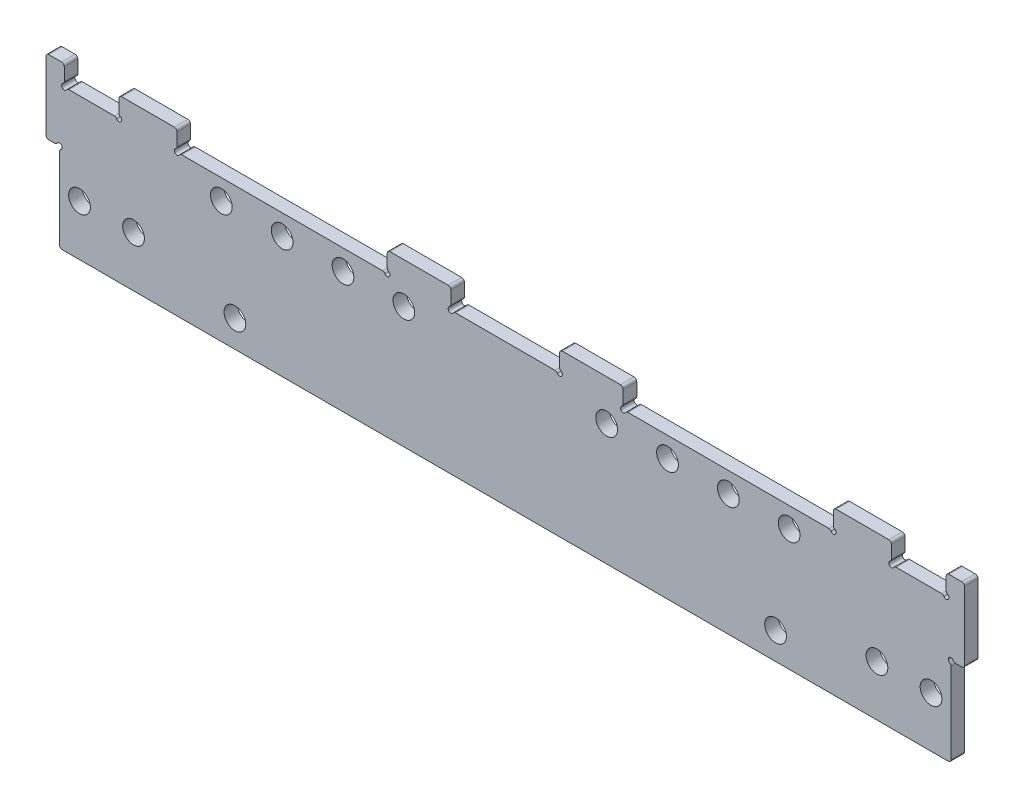
SolidWorks part; units mm, degrees
material "AISI Type A2 Tool Steel"
ref_plane "Front Plane" through (0, 0, 0) normal (0, 0, 1) x (1, 0, 0)
ref_plane "Top Plane" through (0, 0, 0) normal (0, 1, 0) x (1, 0, 0)
ref_plane "Right Plane" through (0, 0, 0) normal (1, 0, 0) x (0, 0, -1)
sketch "Top Layout" plane through (0, 0, 0) normal (0, 1, 0) x (1, 0, 0)
  line L0 (-114.046, -123.825) -> (-104.775, -123.825) construction
  line L1 (-104.775, -142.875) -> (-101.6, -142.875)
  line L2 (-104.775, -142.875) -> (-104.775, -104.775)
  line L3 (-104.775, -104.775) -> (-101.6, -104.775)
  line L4 (-101.6, -142.875) -> (-101.6, -104.775)
  line L5 (-104.775, -142.875) -> (-101.6, -104.775) construction
  line L6 (-104.775, -104.775) -> (-101.6, -142.875) construction
  line L7 (-19.05, -105.8164) -> (-101.6, -105.8164)
  line L8 (-19.05, -105.8164) -> (-19.05, -141.8336)
  line L9 (-19.05, -141.8336) -> (-101.6, -141.8336)
  line L10 (-101.6, -105.8164) -> (-101.6, -141.8336)
  line L11 (-19.05, -105.8164) -> (-101.6, -141.8336) construction
  line L12 (-19.05, -141.8336) -> (-101.6, -105.8164) construction
  line L13 (-133.096, -85.725) -> (-114.046, -85.725)
  line L14 (-133.096, -85.725) -> (-133.096, -161.925)
  line L15 (-133.096, -161.925) -> (-114.046, -161.925)
  line L16 (-114.046, -85.725) -> (-114.046, -161.925)
  line L17 (-133.096, -85.725) -> (-114.046, -161.925) construction
  line L18 (-133.096, -161.925) -> (-114.046, -85.725) construction
  line L19 (-104.775, -123.825) -> (0, -123.825) construction
  line L20 (0, -123.825) -> (0, 0) construction
  line L21 (-52.3528, -40.1717) -> (0, 0) construction
  line L22 (-70.6449, -16.3328) -> (-18.2922, 23.8388)
  line L23 (-34.0606, -64.0105) -> (18.2922, -23.8388)
  line L24 (-30.9251, 40.3023) -> (-122.2248, -29.7544)
  line L25 (-153.9748, -53.975) -> (-153.9748, -123.825)
  line L26 (-109.5248, -162.052) -> (109.5248, -162.052)
  line L27 (0, -162.052) -> (0, -123.825) construction
  line L28 (-109.5248, -162.052) -> (-109.5248, -20.0093) construction
  line L29 (-104.775, -142.875) -> (-104.775, -152.527)
  line L30 (-104.775, -152.527) -> (104.775, -152.527)
  line L31 (104.775, -104.775) -> (101.6, -104.775)
  line L32 (-144.4498, -73.025) -> (-109.5248, -73.025)
  line L33 (-144.4498, -73.025) -> (-144.4498, -123.825)
  line L34 (-144.4498, -123.825) -> (-109.5248, -123.825) construction
  line L35 (-109.5248, -73.025) -> (-109.5248, -162.052)
  line L36 (-144.4498, -73.025) -> (-109.5248, -123.825) construction
  line L37 (-144.4498, -123.825) -> (-109.5248, -73.025) construction
  line L38 (101.6, -142.875) -> (101.6, -104.775)
  line L39 (104.775, -142.875) -> (101.6, -142.875)
  line L40 (104.775, -142.875) -> (104.775, -104.775)
  line L41 (104.775, -142.875) -> (104.775, -152.527)
  line L42 (109.5248, -162.052) -> (109.5248, -20.0093) construction
  line L43 (30.9251, 40.3023) -> (122.2248, -29.7544)
  line L45 (19.05, -141.8336) -> (101.6, -141.8336)
  line L46 (101.6, -105.8164) -> (101.6, -141.8336)
  line L47 (19.05, -105.8164) -> (101.6, -105.8164)
  line L48 (19.05, -105.8164) -> (19.05, -141.8336)
  line L49 (133.096, -161.925) -> (114.046, -161.925)
  line L50 (114.046, -85.725) -> (114.046, -161.925)
  line L51 (133.096, -85.725) -> (114.046, -85.725)
  line L52 (133.096, -85.725) -> (133.096, -161.925)
  line L53 (144.4498, -123.825) -> (109.5248, -123.825) construction
  line L54 (109.5248, -73.025) -> (109.5248, -162.052)
  line L55 (144.4498, -73.025) -> (109.5248, -73.025)
  line L56 (144.4498, -73.025) -> (144.4498, -123.825)
  line L57 (-109.5248, -123.825) -> (-109.5248, -162.052) construction
  line L62 (-153.9748, -53.975) -> (-122.2248, -53.975)
  line L63 (-122.2248, -53.975) -> (-122.2248, -29.7544)
  line L64 (-144.4498, -123.825) -> (-153.9748, -123.825)
  line L65 (153.9748, -53.975) -> (153.9748, -123.825)
  line L66 (109.5248, -123.825) -> (109.5248, -162.052) construction
  line L67 (144.4498, -123.825) -> (153.9748, -123.825)
  line L68 (122.2248, -29.7544) -> (122.2248, -53.975)
  line L73 (-104.775, -104.775) -> (-104.775, -16.3647) construction
  line L74 (-95.25, -162.052) -> (-95.25, -9.0559) construction
  line L75 (-109.5248, -162.052) -> (-109.5248, -123.825) construction
  line L76 (109.5248, -162.052) -> (109.5248, -123.825) construction
  line L77 (122.2248, -53.975) -> (153.9748, -53.975)
  line L83 (104.775, -155.5496) -> (-104.775, -155.5496) construction
  line L88 (95.25, -162.052) -> (95.25, -9.0559) construction
  line L89 (104.775, -104.775) -> (104.775, -16.3647) construction
  line L92 (-104.775, -152.527) -> (-104.775, -162.052) construction
  line L93 (-14.605, -76.327) -> (14.605, -76.327)
  line L94 (-14.605, -76.327) -> (-14.605, -152.527)
  line L95 (-14.605, -152.527) -> (14.605, -152.527)
  line L96 (14.605, -76.327) -> (14.605, -152.527)
  line L97 (-14.605, -76.327) -> (14.605, -152.527) construction
  line L98 (-14.605, -152.527) -> (14.605, -76.327) construction
  line L99 (104.775, -152.527) -> (104.775, -162.052) construction
  line L100 (-19.05, -105.8164) -> (0, -105.8164) construction
  line L107 (0, -105.8164) -> (19.05, -105.8164) construction
  line L108 (104.775, -123.825) -> (114.046, -123.825) construction
  circle A0 centre (0, 0) radius 114.3
  circle A1 centre (0, 0) radius 6.35
  circle A2 centre (-52.3528, -40.1717) radius 17.8
  circle A3 centre (0, 0) radius 30.0482
  circle A4 centre (-52.3528, -40.1717) radius 30.0482
  arc A5 (-30.9251, 40.3023) -> (30.9251, 40.3023) centre (0, 0) cw
  point P2 (-103.1875, -123.825)
  point P7 (-60.325, -123.825)
  point P12 (-123.571, -123.825)
  point P30 (-126.9873, -98.425)
  point P35 (0, -114.427)
  point P53 (0, -152.527)
  dimension "D1" = 35.6
  dimension "D2" = 12.7
  dimension "D3" = 228.6
  dimension "D11" = 60.0964
  dimension "D12" = 50.8
  dimension "D14" = 52.5
  dimension "D4" = 3.175
  dimension "D5" = 19.05
  dimension "D6" = 76.2
  dimension "D7" = 82.55
  dimension "D8" = 38.1
  dimension "D9" = 104.775
  dimension "D10" = 18.0086
  dimension "D13" = 9.525
  dimension "D15" = 4.7498
  dimension "D16" = 9.525
  dimension "D17" = 9.652
  dimension "D18" = 50.8
  dimension "D19" = 12.446
  dimension "D20" = 65.9892
  dimension "D21" = 19.05
  dimension "D22" = 34.925
  dimension "D23" = 123.825
  dimension "D24" = 12.7
  dimension "D25" = 9.525
  dimension "D26" = 29.21
  dimension "D27" = 76.2
  dimension "D28" = 3.0226
sketch "Side Layout" plane through (0, 0, 0) normal (1, 0, 0) x (0, 0, -1)
  line L0 (0, -38.1) -> (0, 33.7344) construction
  line L1 (-114.3, -20.955) -> (114.3, -20.955)
  line L2 (-114.3, -20.955) -> (-114.3, -33.655)
  line L3 (-114.3, -33.655) -> (114.3, -33.655)
  line L4 (114.3, -20.955) -> (114.3, -33.655)
  line L5 (-114.3, -20.955) -> (114.3, -33.655) construction
  line L6 (-114.3, -33.655) -> (114.3, -20.955) construction
  line L7 (-9.525, -32.9406) -> (9.525, -32.9406)
  line L8 (-9.525, -32.9406) -> (-9.525, -38.1)
  line L9 (-9.525, -38.1) -> (9.525, -38.1)
  line L10 (9.525, -32.9406) -> (9.525, -38.1)
  line L11 (-9.525, -32.9406) -> (9.525, -38.1) construction
  line L12 (-9.525, -38.1) -> (9.525, -32.9406) construction
  line L13 (-11.9126, -29.3338) -> (11.9126, -29.3338)
  line L14 (-11.9126, -29.3338) -> (-11.9126, -32.9406)
  line L15 (-11.9126, -32.9406) -> (11.9126, -32.9406)
  line L16 (11.9126, -29.3338) -> (11.9126, -32.9406)
  line L17 (-11.9126, -29.3338) -> (11.9126, -32.9406) construction
  line L18 (-11.9126, -32.9406) -> (11.9126, -29.3338) construction
  line L19 (-6.35, -32.9406) -> (6.35, -32.9406)
  line L20 (-6.35, -32.9406) -> (-6.35, 33.7344)
  line L21 (-6.35, 33.7344) -> (6.35, 33.7344)
  line L22 (6.35, -32.9406) -> (6.35, 33.7344)
  line L23 (-6.35, -32.9406) -> (6.35, 33.7344) construction
  line L24 (-6.35, 33.7344) -> (6.35, -32.9406) construction
  line L25 (-162.052, 0) -> (-123.825, 0) construction
  line L26 (114.3, -33.655) -> (114.3, 0) construction
  line L27 (-142.875, 19.05) -> (-104.775, 19.05)
  line L28 (-40.1717, -9.525) -> (-40.1717, 5.4) construction
  line L29 (-142.875, 19.05) -> (-142.875, -19.05)
  line L30 (-142.875, -19.05) -> (-104.775, -19.05)
  line L31 (-104.775, 19.05) -> (-104.775, -19.05)
  line L32 (-142.875, 19.05) -> (-104.775, -19.05) construction
  line L33 (-142.875, -19.05) -> (-104.775, 19.05) construction
  line L34 (-130.175, -38.1) -> (-117.9516, -38.1) construction
  line L35 (-57.9717, -14.6) -> (-22.3717, -14.6)
  line L36 (-30.0482, -2.794) -> (30.0482, -2.794)
  line L37 (-30.0482, -2.794) -> (-30.0482, -20.955)
  line L38 (-30.0482, -20.955) -> (30.0482, -20.955)
  line L39 (30.0482, -2.794) -> (30.0482, -20.955)
  line L40 (-30.0482, -2.794) -> (30.0482, -20.955) construction
  line L41 (-30.0482, -20.955) -> (30.0482, -2.794) construction
  line L42 (-30.0482, -2.794) -> (-30.0482, 0) construction
  line L43 (-123.825, 0) -> (0, 0) construction
  line L44 (-57.9717, -14.6) -> (-57.9717, 25.4)
  line L45 (-57.9717, 25.4) -> (-22.3717, 25.4)
  line L46 (-22.3717, -14.6) -> (-22.3717, 25.4)
  line L47 (-19.05, 0) -> (19.05, 0)
  line L48 (-19.05, 0) -> (-19.05, -1.9812)
  line L49 (-19.05, -1.9812) -> (19.05, -1.9812)
  line L50 (19.05, 0) -> (19.05, -1.9812)
  line L51 (-19.05, 0) -> (19.05, -1.9812) construction
  line L52 (-19.05, -1.9812) -> (19.05, 0) construction
  line L53 (-70.2199, -3.175) -> (-10.1235, -3.175)
  line L54 (-70.2199, -3.175) -> (-70.2199, -15.875)
  line L55 (-70.2199, -15.875) -> (-10.1235, -15.875)
  line L56 (-10.1235, -3.175) -> (-10.1235, -15.875)
  line L57 (-70.2199, -3.175) -> (-10.1235, -15.875) construction
  line L58 (-70.2199, -15.875) -> (-10.1235, -3.175) construction
  line L59 (-40.1717, -9.525) -> (-40.1717, 0) construction
  line L60 (-57.9717, -14.6) -> (-22.3717, 25.4) construction
  line L61 (-57.9717, 25.4) -> (-22.3717, -14.6) construction
  line L62 (-22.3717, 0) -> (-57.9717, 0) construction
  line L63 (-137.8162, 0) -> (-123.825, -13.9912) construction
  line L64 (-139.065, 15.24) -> (-108.585, 15.24) construction
  line L65 (-139.065, 15.24) -> (-139.065, -15.24) construction
  line L66 (-139.065, -15.24) -> (-108.585, -15.24) construction
  line L67 (-108.585, 15.24) -> (-108.585, -15.24) construction
  line L68 (-139.065, 15.24) -> (-108.585, -15.24) construction
  line L69 (-139.065, -15.24) -> (-108.585, 15.24) construction
  line L70 (-137.8162, 0) -> (-123.825, 13.9912) construction
  line L71 (-123.825, -13.9912) -> (-109.8338, 0) construction
  line L72 (-123.825, 13.9912) -> (-109.8338, 0) construction
  line L73 (-137.8162, 0) -> (-109.8338, 0) construction
  line L74 (-123.825, -13.9912) -> (-123.825, 13.9912) construction
  line L75 (-6.35, 17.8594) -> (6.35, 17.8594)
  line L76 (114.3, 0) -> (-114.3, 0) construction
  line L77 (-22.3717, 19.05) -> (-6.35, 19.05) construction
  line L78 (-123.825, 38.1) -> (-97.9206, 38.1) construction
  line L79 (-19.05, -3.5814) -> (19.05, -3.5814)
  line L80 (-19.05, -3.5814) -> (-19.05, -1.9812)
  line L81 (-19.05, -1.9812) -> (19.05, -1.9812)
  line L82 (19.05, -3.5814) -> (19.05, -1.9812)
  line L83 (-19.05, -3.5814) -> (19.05, -1.9812) construction
  line L84 (-19.05, -1.9812) -> (19.05, -3.5814) construction
  line L85 (-8.7376, -16.7608) -> (8.7376, -16.7608)
  line L86 (-8.7376, -16.7608) -> (-8.7376, -29.3338)
  line L87 (-8.7376, -29.3338) -> (8.7376, -29.3338)
  line L88 (8.7376, -16.7608) -> (8.7376, -29.3338)
  line L89 (-8.7376, -16.7608) -> (8.7376, -29.3338) construction
  line L90 (-8.7376, -29.3338) -> (8.7376, -16.7608) construction
  line L91 (-8.7376, -3.5814) -> (8.7376, -3.5814)
  line L92 (-8.7376, -3.5814) -> (-8.7376, -16.1544)
  line L93 (-8.7376, -16.1544) -> (8.7376, -16.1544)
  line L94 (8.7376, -3.5814) -> (8.7376, -16.1544)
  line L95 (-8.7376, -3.5814) -> (8.7376, -16.1544) construction
  line L96 (-8.7376, -16.1544) -> (8.7376, -3.5814) construction
  circle A0 centre (-123.825, 0) radius 18.0086
  circle A1 centre (-123.825, 0) radius 38.1
  circle A2 centre (-139.065, 15.24) radius 1.905
  circle A3 centre (-108.585, 15.24) radius 1.905
  circle A4 centre (-108.585, -15.24) radius 1.905
  circle A5 centre (-139.065, -15.24) radius 1.905
  circle A6 centre (-137.8162, 0) radius 1.6002
  circle A7 centre (-123.825, 13.9912) radius 1.6002
  circle A8 centre (-109.8338, 0) radius 1.6002
  circle A9 centre (-123.825, -13.9912) radius 1.6002
  point P0 (0, -27.305)
  point P6 (0, -31.1372)
  point P7 (0, -35.5203)
  point P21 (0, 0.3969)
  point P32 (0, -11.8745)
  point P43 (0, -0.9906)
  point P55 (-40.1717, -9.525)
  point P72 (-40.1717, 5.4)
  point P88 (0, -23.0473)
  point P93 (0, -2.7813)
  point P102 (0, -9.8679)
  dimension "D17" = 3.81
  dimension "D18" = 3.2004
  dimension "D1" = 12.7
  dimension "D2" = 5.1594
  dimension "D3" = 19.05
  dimension "D4" = 3.6068
  dimension "D5" = 23.8252
  dimension "D6" = 12.7
  dimension "D7" = 18.161
  dimension "D8" = 1.9812
  dimension "D9" = 12.7
  dimension "D10" = 40
  dimension "D11" = 25.4
  dimension "D12" = 50.8
  dimension "D13" = 41.275
  dimension "D14" = 30.48
  dimension "D15" = 4.445
  dimension "D16" = 19.7866
  dimension "D19" = 15.875
  dimension "D20" = 6.35
  dimension "D21" = 38.1
  dimension "D22" = 1.6002
  dimension "D23" = 38.1
  dimension "D24" = 17.4752
  dimension "D25" = 12.573
ref_plane "Plane1" through (0, 25.4, 0) normal (0, 1, 0) x (1, 0, 0)
sketch "Sketch3" plane through (0, 25.4, 0) normal (0, 1, 0) x (1, 0, 0)
  line L0 (-104.775, -36.3747) -> (-30.9251, 20.2924)
  line L1 (-104.775, -104.775) -> (-104.775, -16.3647) construction
  line L2 (0, -200130.175) -> (0, 199882.0484) construction
  line L3 (-30.9251, 40.3023) -> (-122.2248, -29.7544) construction
  line L5 (-104.775, -36.3747) -> (-104.775, -77.6497)
  line L6 (-92.075, -77.6497) -> (-104.775, -77.6497)
  line L7 (30.9251, 20.2924) -> (104.775, -36.3747)
  line L8 (104.775, -77.6497) -> (92.075, -77.6497)
  line L9 (104.775, -36.3747) -> (104.775, -77.6497)
  line L11 (104.775, -104.775) -> (104.775, -16.3647) construction
  line L12 (30.9251, 40.3023) -> (122.2248, -29.7544) construction
  line L13 (92.075, -74.6536) -> (24.1423, -22.5271)
  line L14 (-32.2514, -66.3682) -> (20.1013, -26.1965)
  line L15 (-30.9251, 20.2924) -> (0, 44.022)
  line L16 (0, 44.022) -> (30.9251, 20.2924)
  line L17 (-92.075, -77.6497) -> (-92.075, -73.1917)
  line L19 (-92.075, -73.1917) -> (-52.3528, -73.1917)
  line L20 (92.075, -74.6536) -> (92.075, -77.6497)
  circle A0 centre (-52.3528, -40.1717) radius 17.8 construction
  circle A1 centre (-52.3528, -40.1717) radius 17.8
  circle A2 centre (0, 0) radius 6.35
  circle A3 centre (0, 0) radius 6.35 construction
  arc A4 (-52.3528, -73.1917) -> (-32.2514, -66.3682) centre (-52.3528, -40.1717) ccw
  arc A5 (20.1013, -26.1965) -> (24.1423, -22.5271) centre (0, 0) ccw
  arc A6 (30.9251, 20.2924) -> (-30.9251, 20.2924) centre (0, -20.01) ccw construction
  point P28 (0, 44.022)
  dimension "D1" = 33.02
  dimension "D5" = 50.8
  dimension "D2" = 41.275
  dimension "D3" = 34.925
  dimension "D4" = 12.7
  dimension "D6" = 38.1
ref_plane "Plane3" through (-104.775, 0, 0) normal (-1, 0, 0) x (0, 0, 1)
sketch "Sketch6" plane through (-104.775, 0, 0) normal (-1, 0, 0) x (0, 0, 1)
  line L0 (162.052, -25.4) -> (162.052, 25.4)
  line L1 (162.052, 25.4) -> (77.6497, 25.4)
  line L2 (36.3747, 25.4) -> (77.6497, 25.4) construction
  line L3 (147.7645, 11.1125) -> (162.052, 11.1125) construction
  line L4 (162.052, 0) -> (71.2997, 0) construction
  line L5 (77.6497, 25.4) -> (77.6497, 19.05)
  line L6 (77.6497, 19.05) -> (36.3747, 19.05)
  line L7 (36.3747, 19.05) -> (36.3747, 6.35)
  line L8 (36.3747, 6.35) -> (71.2997, 6.35)
  line L10 (99.6315, -3.175) -> (99.6315, 11.1125) construction
  line L11 (71.2997, -25.4) -> (162.052, -25.4)
  line L13 (71.2997, 6.35) -> (71.2997, -25.4)
  line L14 (152.527, -25.4) -> (152.527, 25.4) construction
  line L15 (99.6315, 11.1125) -> (99.6315, 25.4) construction
  line L16 (147.7645, 11.1125) -> (147.7645, 25.4) construction
  line L17 (94.869, -7.9375) -> (104.394, -7.9375) construction
  line L18 (94.869, -7.9375) -> (94.869, 25.4) construction
  line L19 (94.869, 25.4) -> (104.394, 25.4) construction
  line L20 (104.394, -7.9375) -> (104.394, 25.4) construction
  line L21 (94.869, -7.9375) -> (104.394, 25.4) construction
  line L22 (94.869, 25.4) -> (104.394, -7.9375) construction
  line L23 (147.7645, 11.1125) -> (147.7645, -3.175) construction
  line L24 (104.394, -7.9375) -> (123.825, -7.9375) construction
  line L25 (143.002, -7.9375) -> (152.527, -7.9375) construction
  line L26 (143.002, -7.9375) -> (143.002, 25.4) construction
  line L27 (143.002, 25.4) -> (152.527, 25.4) construction
  line L28 (152.527, -7.9375) -> (152.527, 25.4) construction
  line L29 (143.002, -7.9375) -> (152.527, 25.4) construction
  line L30 (143.002, 25.4) -> (152.527, -7.9375) construction
  line L31 (123.825, -7.9375) -> (152.527, -7.9375) construction
  line L32 (104.775, 19.05) -> (104.775, -19.05) construction
  line L34 (155.702, -25.4) -> (155.702, 25.4) construction
  circle A0 centre (109.8338, 0) radius 1.6002 construction
  circle A1 centre (123.825, 13.9912) radius 1.6002 construction
  circle A2 centre (137.8162, 0) radius 1.6002 construction
  circle A3 centre (123.825, -13.9912) radius 1.6002 construction
  circle A4 centre (109.8338, 0) radius 1.6002 construction
  circle A5 centre (123.825, 13.9912) radius 1.6002 construction
  circle A6 centre (137.8162, 0) radius 1.6002 construction
  circle A7 centre (123.825, -13.9912) radius 1.6002 construction
  circle A8 centre (123.825, 0) radius 18.0086 construction
  circle A9 centre (123.825, 0) radius 18.0086 construction
  circle A10 centre (123.825, 0) radius 9.525
  circle A11 centre (108.585, -15.24) radius 1.905 construction
  circle A12 centre (108.585, 15.24) radius 1.905 construction
  circle A13 centre (139.065, 15.24) radius 1.905 construction
  circle A14 centre (139.065, -15.24) radius 1.905 construction
  circle A15 centre (108.585, -15.24) radius 1.905
  circle A16 centre (108.585, 15.24) radius 1.905
  circle A17 centre (139.065, 15.24) radius 1.905
  circle A18 centre (139.065, -15.24) radius 1.905
  circle A19 centre (147.7645, 11.1125) radius 2.5527
  circle A26 centre (99.6315, 11.1125) radius 2.5527
  circle A27 centre (99.6315, -3.175) radius 2.5527
  circle A28 centre (147.7645, -3.175) radius 2.5527
  point P29 (0, 0)
  point P55 (99.6315, 8.7312)
  point P61 (147.7645, 8.7312)
  dimension "D4" = 19.05
  dimension "D7" = 5.1054
  dimension "D1" = 6.35
  dimension "D2" = 12.7
  dimension "D3" = 25.4
  dimension "D5" = 6.35
  dimension "D6" = 3.175
  dimension "D8" = 0.381
  dimension "D9" = 14.2875
  dimension "D10" = 9.525
  dimension "D12" = 33.3375
ref_plane "Plane4" through (0, 19.05, 0) normal (0, 1, 0) x (1, 0, 0)
sketch "Sketch12" plane through (0, 19.05, 0) normal (0, 1, 0) x (1, 0, 0)
  line L0 (-104.775, -77.6497) -> (-104.775, -36.3747)
  line L1 (-104.775, -36.3747) -> (-92.075, -36.3747)
  line L3 (-92.075, -36.3747) -> (-92.075, -77.6497)
  line L5 (-92.075, -77.6497) -> (-104.775, -77.6497)
  line L6 (-98.425, -77.6497) -> (-98.425, -63.3622) construction
  line L7 (-98.425, -63.3622) -> (-98.425, -50.6622) construction
  line L8 (-98.425, -50.6622) -> (-98.425, -36.3747) construction
  line L10 (-98.425, -36.3747) -> (-104.775, -36.3747) construction
  circle A0 centre (-98.425, -63.3622) radius 2.5527
  circle A1 centre (-98.425, -50.6622) radius 2.5527
  dimension "D2" = 5.1054
  dimension "D1" = 12.7
  dimension "D3" = 12.7
ref_plane "Plane5" through (0, 0, 152.527) normal (0, 0, 1) x (1, 0, 0)
sketch "Sketch41" plane through (0, 0, 152.527) normal (0, 0, 1) x (1, 0, 0)
  line L0 (-104.775, -7.9375) -> (-104.775, 25.4) construction
  line L1 (-104.775, -7.9375) -> (-104.775, 12.7)
  line L2 (-104.775, -7.9375) -> (104.775, -7.9375)
  line L3 (104.775, -7.9375) -> (104.775, 12.7)
  line L4 (104.775, 25.4) -> (-104.775, 25.4)
  line L5 (0, -7.9375) -> (0, 25.4) construction
  line L6 (-104.775, 3.9624) -> (-100.0125, 3.9624) construction
  line L7 (-100.0125, 3.9624) -> (-100.0125, 25.4) construction
  line L8 (104.775, 3.9624) -> (100.0125, 3.9624) construction
  line L9 (100.0125, 3.9624) -> (100.0125, 25.4) construction
  line L10 (19.05, 20.6375) -> (23.8252, 20.6375) construction
  line L11 (19.05, 15.875) -> (78.5876, 15.875) construction
  line L12 (19.05, 15.875) -> (19.05, 25.4) construction
  line L13 (19.05, 25.4) -> (78.5876, 25.4) construction
  line L14 (78.5876, 15.875) -> (78.5876, 25.4) construction
  line L15 (19.05, 15.875) -> (78.5876, 25.4) construction
  line L16 (19.05, 25.4) -> (78.5876, 15.875) construction
  line L17 (23.8252, 20.6375) -> (38.1127, 20.6375) construction
  line L18 (38.1127, 20.6375) -> (52.4002, 20.6375) construction
  line L19 (52.4002, 20.6375) -> (66.6877, 20.6375) construction
  line L20 (-104.775, 25.4) -> (-112.395, 25.4)
  line L21 (-112.395, 25.4) -> (-112.395, 3.175)
  line L22 (-112.395, 3.175) -> (-109.5248, 3.175)
  line L23 (-109.5248, 3.175) -> (-109.5248, 12.7)
  line L24 (-109.5248, 12.7) -> (-104.775, 12.7)
  line L25 (-104.775, 12.7) -> (-104.775, 25.4) construction
  line L26 (104.775, 25.4) -> (112.395, 25.4)
  line L27 (112.395, 25.4) -> (112.395, 3.175)
  line L28 (112.395, 3.175) -> (109.5248, 3.175)
  line L29 (109.5248, 3.175) -> (109.5248, 12.7)
  line L30 (109.5248, 12.7) -> (104.775, 12.7)
  line L31 (104.775, 12.7) -> (104.775, 25.4) construction
  line L32 (-100.0125, 3.9624) -> (-87.3125, 3.9624) construction
  line L33 (-63.5, -1.5875) -> (0, -1.5875) construction
  line L34 (0, -1.5875) -> (63.5, -1.5875) construction
  line L35 (63.5, -1.5875) -> (63.5, -7.9375) construction
  circle A0 centre (-100.0125, 3.9624) radius 2.5527
  circle A1 centre (100.0125, 3.9624) radius 2.5527
  circle A2 centre (23.8252, 20.6375) radius 2.5527
  circle A3 centre (38.1127, 20.6375) radius 2.5527
  circle A4 centre (52.4002, 20.6375) radius 2.5527
  circle A5 centre (66.6877, 20.6375) radius 2.5527
  circle A6 centre (-66.6877, 20.6375) radius 2.5527
  circle A7 centre (-52.4002, 20.6375) radius 2.5527
  circle A8 centre (-38.1127, 20.6375) radius 2.5527
  circle A9 centre (-23.8252, 20.6375) radius 2.5527
  circle A10 centre (-87.3125, 3.9624) radius 2.5527
  circle A11 centre (87.3125, 3.9624) radius 2.5527
  circle A12 centre (-63.5, -1.5875) radius 2.5527
  circle A13 centre (63.5, -1.5875) radius 2.5527
  point P14 (48.8188, 20.6375)
  dimension "D3" = 5.1054
  dimension "D7" = 5.1054
  dimension "D1" = 21.4376
  dimension "D2" = 4.7625
  dimension "D4" = 9.525
  dimension "D5" = 59.5376
  dimension "D6" = 4.7752
  dimension "D8" = 14.2875
  dimension "D9" = 7.62
  dimension "D10" = 4.7498
  dimension "D11" = 12.7
  dimension "D12" = 9.525
  dimension "D13" = 19.05
  dimension "D14" = 12.7
  dimension "D15" = 6.35
  dimension "D16" = 63.5
extrude "Back Plate Extrude------------" add sketch "Sketch41" along normal blind 3.175
sketch "Sketch44" plane through (0, 25.4, 0) normal (0, 1, 0) x (1, 0, 0)
  line L0 (73.8315, -147.7645) -> (73.8315, -152.527) construction
  line L1 (92.075, -74.6536) -> (92.075, -77.6497) construction
  line L2 (-92.075, -77.6497) -> (-92.075, -73.1917) construction
  line L3 (0, -123.825) -> (0, 0) construction
  line L4 (-92.075, -73.1917) -> (-52.3528, -73.1917) construction
  line L5 (-104.775, -104.775) -> (-104.775, -16.3647) construction
  line L6 (-32.2514, -66.3682) -> (20.1013, -26.1965) construction
  line L21 (-104.775, -68.1247) -> (-104.775, -152.527)
  line L22 (-104.775, -152.527) -> (104.775, -152.527)
  line L23 (104.775, -152.527) -> (104.775, -68.1247)
  line L34 (-104.775, -99.6315) -> (-100.0125, -99.6315) construction
  line L35 (-104.775, -147.7645) -> (-100.0125, -147.7645) construction
  line L36 (0, -152.527) -> (0, -35.6178) construction
  line L38 (30.969, -147.7645) -> (45.2565, -147.7645) construction
  line L39 (45.2565, -147.7645) -> (59.544, -147.7645) construction
  line L40 (59.544, -147.7645) -> (73.8315, -147.7645) construction
  line L41 (23.8252, -152.527) -> (30.969, -152.527) construction
  line L42 (104.775, -152.527) -> (-104.775, -152.527) construction
  line L43 (30.969, -152.527) -> (38.1127, -152.527) construction
  line L44 (30.969, -152.527) -> (30.969, -147.7645) construction
  line L45 (-92.075, -77.6497) -> (-104.775, -77.6497) construction
  line L48 (-35.1507, -62.5899) -> (-8.9743, -42.504) construction
  line L49 (-8.9743, -42.504) -> (17.2021, -22.4182) construction
  line L50 (45.5313, -32.9364) -> (87.3125, -64.9962) construction
  line L51 (92.075, -74.6536) -> (24.1423, -22.5271) construction
  line L52 (104.775, -77.6497) -> (92.075, -77.6497) construction
  line L79 (-104.775, -68.1247) -> (-92.075, -68.1247)
  line L80 (-92.075, -68.1247) -> (-92.075, -63.6667)
  line L85 (21.8118, -8.7328) -> (92.075, -62.6476)
  line L86 (-38.0499, -58.8115) -> (14.3028, -18.6398)
  line L87 (-92.075, -63.6667) -> (-52.3528, -63.6667)
  line L88 (92.075, -62.6476) -> (92.075, -68.1247)
  line L89 (92.075, -68.1247) -> (104.775, -68.1247)
  circle A0 centre (-73.8315, -147.7645) radius 2.5527
  circle A1 centre (-59.544, -147.7645) radius 2.5527
  circle A2 centre (-45.2565, -147.7645) radius 2.5527
  circle A3 centre (-30.969, -147.7645) radius 2.5527
  circle A17 centre (-100.0125, -99.6315) radius 2.5527
  circle A18 centre (-100.0125, -147.7645) radius 2.5527
  circle A19 centre (100.0125, -147.7645) radius 2.5527
  circle A20 centre (100.0125, -99.6315) radius 2.5527
  circle A21 centre (30.969, -147.7645) radius 2.5527
  circle A22 centre (45.2565, -147.7645) radius 2.5527
  circle A23 centre (59.544, -147.7645) radius 2.5527
  circle A24 centre (73.8315, -147.7645) radius 2.5527
  circle A25 centre (-87.3125, -68.4292) radius 4.7625 construction
  circle A26 centre (-35.1507, -62.5899) radius 4.7625 construction
  circle A27 centre (-8.9743, -42.504) radius 4.7625 construction
  circle A28 centre (17.2021, -22.4182) radius 4.7625 construction
  circle A29 centre (45.5313, -32.9364) radius 4.7625 construction
  circle A30 centre (87.3125, -64.9962) radius 4.7625 construction
  circle A32 centre (-87.3125, -68.4292) radius 2.5527
  circle A33 centre (-35.1507, -62.5899) radius 2.5527
  circle A34 centre (-8.9743, -42.504) radius 2.5527 construction
  circle A35 centre (17.2021, -22.4182) radius 2.5527
  circle A36 centre (45.5313, -32.9364) radius 2.5527
  circle A37 centre (87.3125, -64.9962) radius 2.5527
  circle A38 centre (-97.155, -85.2697) radius 7.62 construction
  circle A39 centre (97.155, -85.2697) radius 7.62 construction
  circle A40 centre (24.5121, -32.4156) radius 7.62 construction
  arc A41 (20.1013, -26.1965) -> (24.1423, -22.5271) centre (0, 0) ccw construction
  circle A42 centre (-97.155, -85.2697) radius 2.5527
  circle A43 centre (24.5121, -32.4156) radius 2.5527
  circle A44 centre (97.155, -85.2697) radius 2.5527
  arc A56 (14.3028, -18.6398) -> (21.8118, -8.7328) centre (0, 0) ccw
  arc A57 (-52.3528, -63.6667) -> (-38.0499, -58.8115) centre (-52.3528, -40.1717) ccw
  point P4 (-104.775, -152.527)
  dimension "D2" = 5.1054
  dimension "D7" = 5.1054
  dimension "D8" = 15.24
  dimension "D3" = 9.525
  dimension "D9" = 9.525
  dimension "D4" = 4.7625
  dimension "D5" = 14.2875
  dimension "D6" = 9.525
  dimension "D1" = 4.7625
  dimension "D10" = 52.664
sketch "Sketch72" plane through (0, 25.4, 0) normal (0, 1, 0) x (1, 0, 0)
  line L0 (-104.775, -68.1247) -> (-104.775, -152.527) construction
  line L1 (-104.775, -152.527) -> (-109.5248, -152.527)
  line L2 (-104.775, -152.527) -> (-104.775, -135.0645)
  line L3 (-104.775, -135.0645) -> (-109.5248, -135.0645)
  line L4 (-109.5248, -152.527) -> (-109.5248, -135.0645)
  line L5 (-104.775, -152.527) -> (-109.5248, -135.0645) construction
  line L6 (-104.775, -135.0645) -> (-109.5248, -152.527) construction
  line L7 (-104.775, -152.527) -> (104.775, -152.527) construction
  line L8 (-77.0065, -152.527) -> (-73.8315, -147.7645) construction
  line L9 (-77.0065, -152.527) -> (-27.794, -152.527)
  line L10 (-77.0065, -152.527) -> (-77.0065, -155.5496)
  line L11 (-77.0065, -155.5496) -> (-27.794, -155.5496)
  line L12 (-27.794, -152.527) -> (-27.794, -155.5496)
  line L13 (-77.0065, -152.527) -> (-27.794, -155.5496) construction
  line L14 (-77.0065, -155.5496) -> (-27.794, -152.527) construction
  line L15 (-27.794, -152.527) -> (-30.969, -147.7645) construction
  line L16 (-77.0065, -152.527) -> (-77.0065, -147.7645) construction
  line L18 (-104.775, -93.5247) -> (-109.5248, -93.5247)
  line L19 (-104.775, -93.5247) -> (-104.775, -112.3315)
  line L20 (-104.775, -112.3315) -> (-109.5248, -112.3315)
  line L21 (-109.5248, -93.5247) -> (-109.5248, -112.3315)
  line L22 (-104.775, -93.5247) -> (-109.5248, -112.3315) construction
  line L23 (-104.775, -112.3315) -> (-109.5248, -93.5247) construction
  line L24 (0, -152.527) -> (-12.7, -152.527)
  line L25 (0, -152.527) -> (0, -155.5496)
  line L26 (0, -155.5496) -> (-12.7, -155.5496)
  line L27 (-12.7, -152.527) -> (-12.7, -155.5496)
  line L28 (0, -152.527) -> (-12.7, -155.5496) construction
  line L29 (0, -155.5496) -> (-12.7, -152.527) construction
  line L30 (-104.775, -68.1247) -> (-109.5248, -68.1247)
  line L31 (-104.775, -68.1247) -> (-104.775, -77.6497)
  line L32 (-104.775, -77.6497) -> (-109.5248, -77.6497)
  line L33 (-109.5248, -68.1247) -> (-109.5248, -77.6497)
  line L34 (-104.775, -68.1247) -> (-109.5248, -77.6497) construction
  line L35 (-104.775, -77.6497) -> (-109.5248, -68.1247) construction
  line L38 (-103.505, -155.5496) -> (-90.805, -155.5496)
  line L39 (-90.805, -152.527) -> (-90.805, -155.5496)
  line L40 (-103.505, -155.5496) -> (-103.505, -152.527)
  line L41 (-103.505, -155.5496) -> (-90.805, -152.527) construction
  line L42 (-103.505, -152.527) -> (-90.805, -152.527)
  line L43 (-77.0065, -147.7645) -> (-73.8315, -147.7645) construction
  line L44 (-103.505, -152.527) -> (-101.5221, -149.823) construction
  circle A0 centre (-100.0125, -147.7645) radius 2.5527 construction
  circle A1 centre (-73.8315, -147.7645) radius 2.5527 construction
  circle A2 centre (-30.969, -147.7645) radius 2.5527 construction
  point P4 (-107.1499, -143.7958)
  point P5 (-100.0125, -147.7645)
  point P16 (-52.4002, -154.0383)
  point P18 (-97.155, -154.0383)
  point P25 (-107.1499, -102.9281)
  point P34 (-6.35, -154.0383)
  point P39 (-107.1499, -72.8872)
  dimension "D1" = 4.7498
  dimension "D2" = 12.7
  dimension "D3" = 12.7
  dimension "D4" = 12.7
  dimension "D5" = 9.525
  dimension "D6" = 15.875
  dimension "D7" = 12.7
  dimension "D8" = 3.175
  dimension "D9" = 1.27
  dimension "D10" = 3.0226
sketch "Sketch71" plane through (0, 0, 155.702) normal (0, 0, 1) x (1, 0, 0)
  line L1 (-112.395, 25.4) -> (-103.505, 25.4)
  line L2 (-112.395, 25.4) -> (-112.395, 30.1625)
  line L3 (-112.395, 30.1625) -> (-103.505, 30.1625)
  line L4 (-103.505, 25.4) -> (-103.505, 30.1625)
  line L5 (-112.395, 25.4) -> (-103.505, 30.1625) construction
  line L6 (-112.395, 30.1625) -> (-103.505, 25.4) construction
  line L13 (112.395, 25.4) -> (-112.395, 25.4) construction
  line L15 (-90.805, 25.4) -> (-77.0065, 25.4)
  line L16 (-90.805, 25.4) -> (-90.805, 30.1625)
  line L17 (-90.805, 30.1625) -> (-77.0065, 30.1625)
  line L18 (-77.0065, 25.4) -> (-77.0065, 30.1625)
  line L19 (-90.805, 25.4) -> (-77.0065, 30.1625) construction
  line L20 (-90.805, 30.1625) -> (-77.0065, 25.4) construction
  line L21 (-27.794, 25.4) -> (-12.7, 25.4)
  line L22 (-27.794, 25.4) -> (-27.794, 30.1625)
  line L23 (-27.794, 30.1625) -> (-12.7, 30.1625)
  line L24 (-12.7, 25.4) -> (-12.7, 30.1625)
  line L25 (-27.794, 25.4) -> (-12.7, 30.1625) construction
  line L26 (-27.794, 30.1625) -> (-12.7, 25.4) construction
  point P4 (-107.95, 27.7812)
  point P20 (-83.9057, 27.7812)
  point P25 (-20.247, 27.7812)
  dimension "D1" = 4.7625
extrude "Boss-Extrude26" add sketch "Sketch71" against normal through all
mirror "Mirror23" about plane through (0, 0, 0) normal (1, 0, 0) of "Boss-Extrude26"
sketch "Sketch91" plane through (0, 0, 152.527) normal (0, 0, -1) x (-1, 0, 0)
  line L1 (-109.601, -7.9375) -> (-104.6988, -7.9375)
  line L2 (-109.601, -7.9375) -> (-109.601, 12.827)
  line L3 (-109.601, 12.827) -> (-104.6988, 12.827)
  line L4 (-104.6988, -7.9375) -> (-104.6988, 12.827)
  line L5 (-109.601, -7.9375) -> (-104.6988, 12.827) construction
  line L6 (-109.601, 12.827) -> (-104.6988, -7.9375) construction
  line L8 (-109.5248, 12.7) -> (-109.5248, 3.175) construction
  line L9 (104.775, -7.9375) -> (-104.775, -7.9375) construction
  line L10 (-103.505, 30.1625) -> (-112.395, 30.1625) construction
  line L11 (-103.5812, 30.1625) -> (-90.7288, 30.1625)
  line L12 (-103.5812, 30.1625) -> (-103.5812, 25.4)
  line L13 (-103.5812, 25.4) -> (-90.7288, 25.4)
  line L14 (-90.7288, 30.1625) -> (-90.7288, 25.4)
  line L15 (-103.5812, 30.1625) -> (-90.7288, 25.4) construction
  line L16 (-103.5812, 25.4) -> (-90.7288, 30.1625) construction
  line L17 (-103.505, 25.4) -> (-90.805, 25.4) construction
  line L18 (-103.505, 25.4) -> (-103.505, 30.1625) construction
  line L19 (-77.0065, 30.1625) -> (-90.805, 30.1625) construction
  line L20 (-77.0827, 30.1625) -> (-27.7178, 30.1625)
  line L21 (-77.0827, 30.1625) -> (-77.0827, 25.4)
  line L22 (-77.0827, 25.4) -> (-27.7178, 25.4)
  line L23 (-27.7178, 30.1625) -> (-27.7178, 25.4)
  line L24 (-77.0827, 30.1625) -> (-27.7178, 25.4) construction
  line L25 (-77.0827, 25.4) -> (-27.7178, 30.1625) construction
  line L26 (-77.0065, 25.4) -> (-27.794, 25.4) construction
  line L27 (-77.0065, 25.4) -> (-77.0065, 30.1625) construction
  line L28 (-12.7, 25.4) -> (12.7, 25.4) construction
  line L29 (0, 25.4) -> (-12.7762, 25.4)
  line L30 (0, 25.4) -> (0, 30.1625)
  line L31 (0, 30.1625) -> (-12.7762, 30.1625)
  line L32 (-12.7762, 25.4) -> (-12.7762, 30.1625)
  line L33 (0, 25.4) -> (-12.7762, 30.1625) construction
  line L34 (0, 30.1625) -> (-12.7762, 25.4) construction
  line L35 (-12.7, 30.1625) -> (-27.794, 30.1625) construction
  line L36 (-12.7, 25.4) -> (-12.7, 30.1625) construction
  line L37 (-107.1499, 12.7) -> (-107.1499, 12.827) construction
  line L38 (-104.775, 12.7) -> (-109.5248, 12.7) construction
  point P4 (-107.1499, 2.4447)
  point P18 (-97.155, 27.7812)
  point P22 (-97.155, 25.4)
  point P23 (-97.155, 25.4)
  point P30 (-52.4002, 27.7812)
  point P35 (-52.4002, 25.4)
  point P36 (-52.4002, 25.4)
  point P43 (-6.3881, 27.7812)
  dimension "D1" = 0.0762
  dimension "D2" = 0.0762
  dimension "D3" = 0.0762
  dimension "D4" = 0.0762
  dimension "D5" = 0.127
extrude "Back Plate Tolerences" cut sketch "Sketch91" against normal through all
mirror "Mirror25" about plane through (0, 0, 0) normal (1, 0, 0) of "Back Plate Tolerences"
sketch "Sketch92" plane through (0, 0, 155.702) normal (0, 0, 1) x (1, 0, 0)
  line L0 (-104.6988, -7.9375) -> (-104.6988, 12.827) construction
  line L1 (-112.395, 30.1625) -> (-107.8738, 30.1625)
  line L2 (-112.395, 30.1625) -> (-112.395, 3.175)
  line L3 (-112.395, 3.175) -> (-107.8738, 3.175)
  line L4 (-107.8738, 30.1625) -> (-107.8738, 3.175)
  line L5 (-112.395, 30.1625) -> (-107.8738, 3.175) construction
  line L6 (-112.395, 3.175) -> (-107.8738, 30.1625) construction
  line L7 (112.395, 30.1625) -> (107.8738, 30.1625)
  line L8 (112.395, 30.1625) -> (112.395, 3.175)
  line L9 (112.395, 3.175) -> (107.8738, 3.175)
  line L10 (107.8738, 30.1625) -> (107.8738, 3.175)
  line L11 (112.395, 30.1625) -> (107.8738, 3.175) construction
  line L12 (112.395, 3.175) -> (107.8738, 30.1625) construction
  point P4 (-110.1344, 16.6687)
  point P11 (110.1344, 16.6687)
  point P16 (-107.8738, 0.8459)
  point P17 (-112.395, 3.175)
  point P19 (112.395, 3.175)
  dimension "D1" = 3.175
extrude "Cut-Extrude1" cut sketch "Sketch92" against normal through all
fillet "Fillet27" radius 0.635 6 edges at (-104.6988, -7.9375, 154.1145) (104.6988, -7.9375, 154.1145) (107.8738, 12.827, 154.1145) (107.8738, 30.1625, 154.1145) (-107.8738, 12.827, 154.1145) (-107.8738, 30.1625, 154.1145)
fillet "Fillet28" radius 0.635 10 edges at (103.5812, 30.1625, 154.1145) (90.7288, 30.1625, 154.1145) (77.0827, 30.1625, 154.1145) (27.7178, 30.1625, 154.1145) (12.7762, 30.1625, 154.1145) (-12.7762, 30.1625, 154.1145) (-27.7178, 30.1625, 154.1145) (-77.0827, 30.1625, 154.1145) (-90.7288, 30.1625, 154.1145) (-103.5812, 30.1625, 154.1145)
sketch "Sketch93" plane through (0, 0, 155.702) normal (0, 0, 1) x (1, 0, 0)
  circle A0 centre (-104.6988, 12.827) radius 0.635
  circle A1 centre (-103.5812, 25.4) radius 0.635
  circle A2 centre (-90.7288, 25.4) radius 0.635
  circle A3 centre (-77.0827, 25.4) radius 0.635
  circle A4 centre (-27.7178, 25.4) radius 0.635
  circle A5 centre (-12.7762, 25.4) radius 0.635
  dimension "D1" = 1.27
extrude "Cut-Extrude2" cut sketch "Sketch93" against normal through all
fillet "Fillet29" radius 0.635 12 edges at (-12.1412, 25.4, 154.1145) (-12.7762, 26.035, 154.1145) (-27.7178, 26.035, 154.1145) (-28.3528, 25.4, 154.1145) (-76.4477, 25.4, 154.1145) (-77.0827, 26.035, 154.1145) (-90.7288, 26.035, 154.1145) (-91.3638, 25.4, 154.1145) (-103.5812, 26.035, 154.1145) (-102.9462, 25.4, 154.1145) (-105.3338, 12.827, 154.1145) (-104.6988, 12.192, 154.1145)
mirror "Mirror26" about plane through (0, 0, 0) normal (1, 0, 0) of "Cut-Extrude2", "Fillet29"
